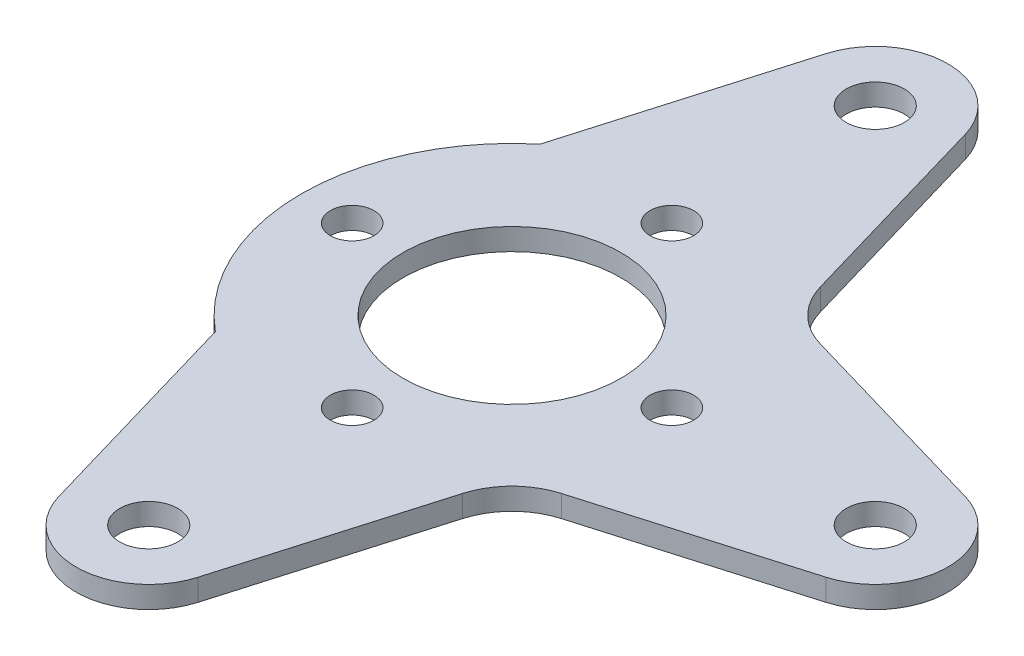
SolidWorks part; units mm, degrees
material "201 Stal nierdzewna odprężona (SS)"
ref_plane "Płaszczyzna przednia" through (0, 0, 0) normal (0, 0, 1) x (1, 0, 0)
ref_plane "Płaszczyzna górna" through (0, 0, 0) normal (0, 1, 0) x (1, 0, 0)
ref_plane "Płaszczyzna prawa" through (0, 0, 0) normal (1, 0, 0) x (0, 0, -1)
sketch "Szkic1" plane through (0, 0, 0) normal (0, 1, 0) x (1, 0, 0)
  line L0 (2.3194, -24.6194) -> (-5.9, -52.8)
  line L1 (9.1194, -17.8194) -> (37.3, -9.6)
  line L2 (9.1194, 17.8194) -> (37.3, 9.6)
  line L3 (2.3194, 24.6194) -> (-5.9, 52.8)
  line L4 (-33.9819, 22.3477) -> (-25.1, 52.8)
  line L5 (-33.9819, -22.3477) -> (-25.1, -52.8)
  circle A0 centre (-15.5, -50) radius 4
  arc A1 (9.1194, -17.8194) -> (2.3194, -24.6194) centre (11.9194, -27.4194) ccw
  arc A2 (37.3, -9.6) -> (37.3, 9.6) centre (34.5, 0) ccw
  arc A3 (2.3194, 24.6194) -> (9.1194, 17.8194) centre (11.9194, 27.4194) ccw
  arc A4 (-5.9, 52.8) -> (-25.1, 52.8) centre (-15.5, 50) ccw
  circle A5 centre (-15.5, 50) radius 4
  circle A6 centre (-37.5, 0) radius 3
  circle A7 centre (-15.5, -22) radius 3
  circle A8 centre (6.5, 0) radius 3
  circle A9 centre (-15.5, 22) radius 3
  circle A10 centre (34.5, 0) radius 4
  circle A11 centre (-15.5, 0) radius 15
  arc A12 (-25.1, -52.8) -> (-5.9, -52.8) centre (-15.5, -50) ccw
  arc A13 (-33.9819, 22.3477) -> (-33.9819, -22.3477) centre (-15.5, 0) ccw
extrude "Dodanie-wyciągnięcie1" add sketch "Szkic1" along normal blind 3
